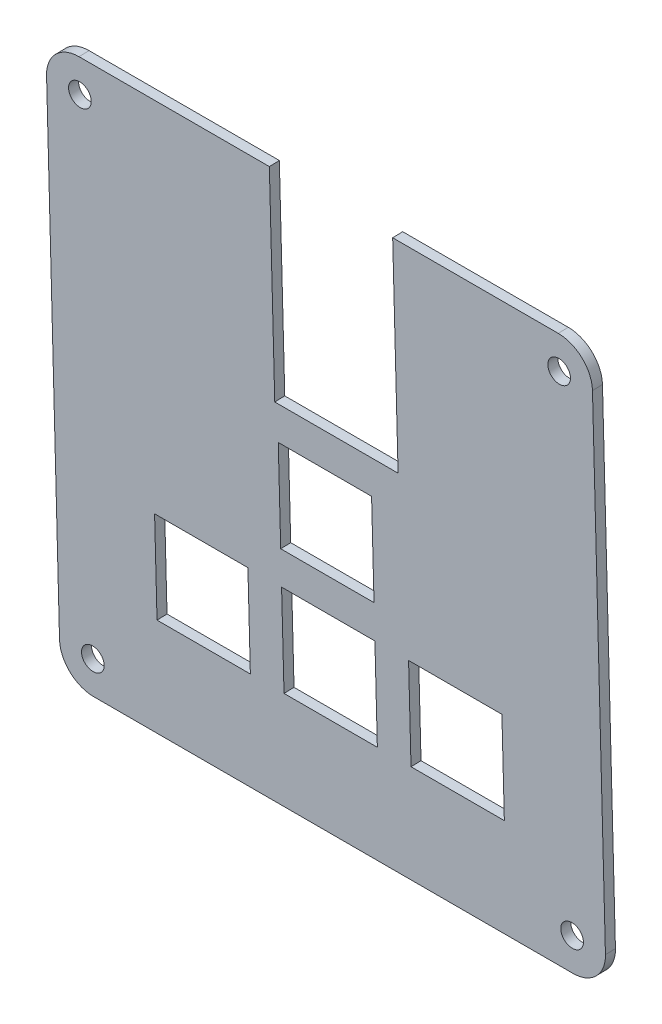
SolidWorks part; units mm, degrees
ref_plane "Front Plane" through (0, 0, 0) normal (0, 0, 1) x (1, 0, 0)
ref_plane "Top Plane" through (0, 0, 0) normal (0, 1, 0) x (1, 0, 0)
ref_plane "Right Plane" through (0, 0, 0) normal (1, 0, 0) x (0, 0, -1)
sketch "Sketch1" plane through (0, 0, 0) normal (0, 1, 0) x (1, 0, 0)
  line L0 (-6.7208, 16.4146) -> (6.2792, 16.4146)
  line L1 (-6.7208, 2.4146) -> (6.2792, 2.4146)
  line L2 (-7.2208, 15.9146) -> (-7.2208, 2.9146)
  line L3 (6.7792, 15.9146) -> (6.7792, 2.9146)
  line L4 (-25.7708, -2.6354) -> (-12.7708, -2.6354)
  line L5 (-25.7708, -16.6354) -> (-12.7708, -16.6354)
  line L6 (-26.2708, -3.1354) -> (-26.2708, -16.1354)
  line L7 (-12.2708, -3.1354) -> (-12.2708, -16.1354)
  line L8 (-6.7208, -2.6354) -> (6.2792, -2.6354)
  line L9 (-6.7208, -16.6354) -> (6.2792, -16.6354)
  line L10 (-7.2208, -3.1354) -> (-7.2208, -16.1354)
  line L11 (6.7792, -3.1354) -> (6.7792, -16.1354)
  line L12 (12.3292, -2.6354) -> (25.3292, -2.6354)
  line L13 (12.3292, -16.6354) -> (25.3292, -16.6354)
  line L14 (11.8292, -3.1354) -> (11.8292, -16.1354)
  line L15 (25.8292, -3.1354) -> (25.8292, -16.1354)
  arc A0 (-6.7208, 16.4146) -> (-7.2208, 15.9146) centre (-6.7208, 15.9146) ccw
  arc A1 (6.7792, 15.9146) -> (6.2792, 16.4146) centre (6.2792, 15.9146) ccw
  arc A2 (-7.2208, 2.9146) -> (-6.7208, 2.4146) centre (-6.7208, 2.9146) ccw
  arc A3 (6.2792, 2.4146) -> (6.7792, 2.9146) centre (6.2792, 2.9146) ccw
  arc A4 (-25.7708, -2.6354) -> (-26.2708, -3.1354) centre (-25.7708, -3.1354) ccw
  arc A5 (-12.2708, -3.1354) -> (-12.7708, -2.6354) centre (-12.7708, -3.1354) ccw
  arc A6 (-26.2708, -16.1354) -> (-25.7708, -16.6354) centre (-25.7708, -16.1354) ccw
  arc A7 (-12.7708, -16.6354) -> (-12.2708, -16.1354) centre (-12.7708, -16.1354) ccw
  arc A8 (-6.7208, -2.6354) -> (-7.2208, -3.1354) centre (-6.7208, -3.1354) ccw
  arc A9 (6.7792, -3.1354) -> (6.2792, -2.6354) centre (6.2792, -3.1354) ccw
  arc A10 (-7.2208, -16.1354) -> (-6.7208, -16.6354) centre (-6.7208, -16.1354) ccw
  arc A11 (6.2792, -16.6354) -> (6.7792, -16.1354) centre (6.2792, -16.1354) ccw
  arc A12 (12.3292, -2.6354) -> (11.8292, -3.1354) centre (12.3292, -3.1354) ccw
  arc A13 (25.8292, -3.1354) -> (25.3292, -2.6354) centre (25.3292, -3.1354) ccw
  arc A14 (11.8292, -16.1354) -> (12.3292, -16.6354) centre (12.3292, -16.1354) ccw
  arc A15 (25.3292, -16.6354) -> (25.8292, -16.1354) centre (25.3292, -16.1354) ccw
  dimension "D7" = 25.8292
  dimension "D1" = 2.4146
  dimension "D2" = 5.05
  dimension "D3" = 5.05
  dimension "D4" = 5.05
  dimension "D5" = 14
  dimension "D6" = 14
sketch "Sketch2" plane through (0, 0, 0) normal (0, 1, 0) x (1, 0, 0)
  line L1 (41.1982, 53.2236) -> (-40.6918, 53.2236)
  line L2 (41.1982, 53.2236) -> (41.1982, -31.0564)
  line L3 (41.1982, -31.0564) -> (-40.6918, -31.0564)
  line L4 (-40.6918, 53.2236) -> (-40.6918, -31.0564)
  line L5 (41.1982, 53.2236) -> (-40.6918, -31.0564) construction
  line L6 (41.1982, -31.0564) -> (-40.6918, 53.2236) construction
  line L12 (-25.7708, -16.6354) -> (-12.7708, -16.6354) construction
  line L13 (-26.2708, -3.1354) -> (-26.2708, -16.1354) construction
  line L16 (-10.8518, 53.2236) -> (7.6482, 53.2236)
  line L17 (-10.8518, 53.2236) -> (-10.8518, 22.2236)
  line L18 (-10.8518, 22.2236) -> (7.6482, 22.2236)
  line L19 (7.6482, 53.2236) -> (7.6482, 22.2236)
  circle A0 centre (36.1982, 48.2236) radius 1.7
  circle A1 centre (-35.6918, 48.2236) radius 1.7
  circle A2 centre (-35.6918, -26.0564) radius 1.7
  circle A3 centre (36.1982, -26.0564) radius 1.7
  point P0 (0, 0)
  point P22 (0, 0)
  dimension "D8" = 3.4
  dimension "D9" = 3.4
  dimension "D10" = 3.4
  dimension "D11" = 3.4
  dimension "D1" = 81.89
  dimension "D2" = 84.28
  dimension "D3" = 14.421
  dimension "D4" = 14.421
  dimension "D5" = 18.5
  dimension "D6" = 31
  dimension "D7" = 29.84
  dimension "D12" = 5
  dimension "D13" = 5
  dimension "D14" = 5
  dimension "D15" = 5
  dimension "D16" = 5
  dimension "D17" = 5
  dimension "D18" = 5
  dimension "D19" = 5
extrude "Boss-Extrude3" add sketch "Sketch2" along normal blind 1.5 contours L1 L19 L18 L17 L4 L3 L2 A3 A2 A1 A0 region at (0.4223, 0, -8.6554)
extrude "Cut-Extrude5" [suppressed] cut sketch "Sketch1" against normal blind 4.5 and the other way blind 7
fillet "Fillet4" radius 5 4 edges at (-40.6918, 0.75, 31.0564) (41.1982, 0.75, 31.0564) (41.1982, 0.75, -53.2236) (-40.6918, 0.75, -53.2236)
move or copy body "Body-Move/Copy1" bodies to move or copy 103 copy no rotation origin (0, 0.75, -12.2836) rotation axis (-1, 0, 0) rotation angle 91.5
move or copy body "Body-Move/Copy2" bodies to move or copy 106 copy no rotation origin (0.4032, 0.75, 0) rotation axis (0, 0, 1) rotation angle 180
sketch "Sketch3" plane through (0, 0.3416, -13.0445) normal (0, 0.0262, -0.9997) x (-1, 0, 0)
  line L0 (-41.4982, 36.3682) -> (-41.4982, -37.9118) construction
  line L1 (-26.5982, -13.8118) -> (-12.5982, -13.8118)
  line L2 (-26.5982, -13.8118) -> (-26.5982, -27.8118)
  line L3 (-26.5982, -27.8118) -> (-12.5982, -27.8118)
  line L4 (-12.5982, -13.8118) -> (-12.5982, -27.8118)
  line L5 (-7.5482, -13.8118) -> (6.4518, -13.8118)
  line L6 (-7.5482, -13.8118) -> (-7.5482, -27.8118)
  line L7 (-7.5482, -27.8118) -> (6.4518, -27.8118)
  line L8 (6.4518, -13.8118) -> (6.4518, -27.8118)
  line L9 (11.5018, -13.8118) -> (25.5018, -13.8118)
  line L10 (11.5018, -13.8118) -> (11.5018, -27.8118)
  line L11 (11.5018, -27.8118) -> (25.5018, -27.8118)
  line L12 (25.5018, -13.8118) -> (25.5018, -27.8118)
  line L13 (-7.5482, 5.2382) -> (6.4518, 5.2382)
  line L14 (-7.5482, 5.2382) -> (-7.5482, -8.7618)
  line L15 (-7.5482, -8.7618) -> (6.4518, -8.7618)
  line L16 (6.4518, 5.2382) -> (6.4518, -8.7618)
  line L17 (35.3918, -42.9118) -> (-36.4982, -42.9118) construction
  dimension "D1" = 14
  dimension "D2" = 14
  dimension "D3" = 14
  dimension "D4" = 14
  dimension "D5" = 14
  dimension "D6" = 14
  dimension "D7" = 14
  dimension "D8" = 14
  dimension "D9" = 5.05
  dimension "D10" = 5.05
  dimension "D11" = 5.05
  dimension "D12" = 5.05
  dimension "D13" = 5.05
  dimension "D14" = 5.05
  dimension "D15" = 14.9
  dimension "D16" = 15.1
extrude "Cut-Extrude6" cut sketch "Sketch3" against normal blind 10
